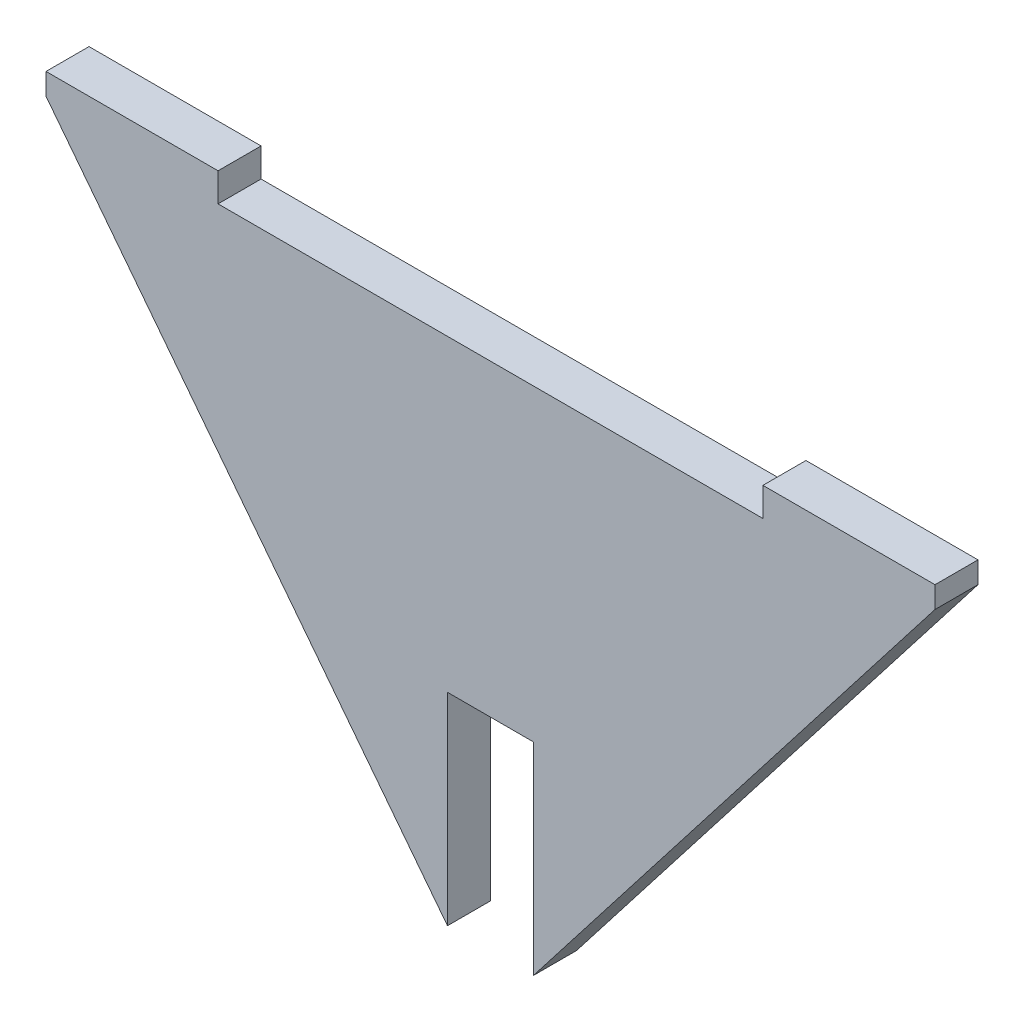
SolidWorks part; units mm, degrees
ref_plane "Plan de face" through (0, 0, 0) normal (0, 0, 1) x (1, 0, 0)
ref_plane "Plan de dessus" through (0, 0, 0) normal (0, 1, 0) x (1, 0, 0)
ref_plane "Plan de droite" through (0, 0, 0) normal (1, 0, 0) x (0, 0, -1)
sketch "Esquisse1" plane through (0, 0, 0) normal (0, 0, 1) x (1, 0, 0)
  line L0 (-11.5828, 14.7071) -> (26.4172, 14.7071)
  line L1 (26.4172, 14.7071) -> (26.4172, 16.7071)
  line L2 (26.4172, 16.7071) -> (38.4172, 16.7071)
  line L3 (38.4172, 16.7071) -> (38.4172, 15.2071)
  line L4 (38.4172, 15.2071) -> (10.4172, -20.8929)
  line L5 (10.4172, -20.8929) -> (10.4172, -6.7929)
  line L6 (10.4172, -6.7929) -> (4.4172, -6.7929)
  line L7 (7.4172, -6.7929) -> (7.4172, 14.7071) construction
  line L8 (4.4172, -20.8929) -> (4.4172, -6.7929)
  line L9 (-23.5828, 15.2071) -> (4.4172, -20.8929)
  line L10 (-23.5828, 16.7071) -> (-23.5828, 15.2071)
  line L11 (-11.5828, 16.7071) -> (-23.5828, 16.7071)
  line L12 (-11.5828, 14.7071) -> (-11.5828, 16.7071)
  dimension "D1" = 2
  dimension "D2" = 12
  dimension "D3" = 1.5
  dimension "D4" = 21.5
  dimension "D5" = 6
  dimension "D6" = 38
  dimension "D7" = 14.1
extrude "Boss.-Extru.1" add sketch "Esquisse1" along normal blind 3
